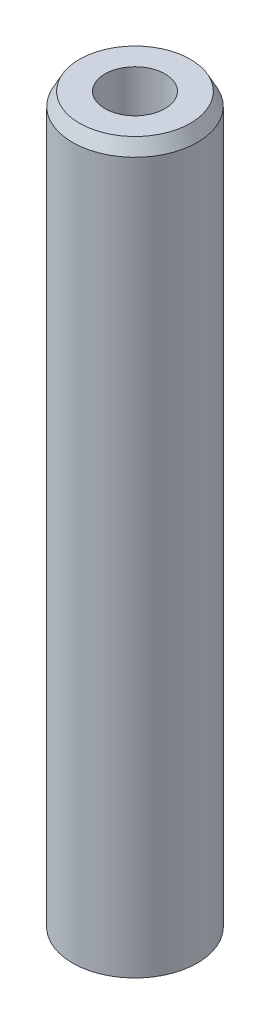
SolidWorks part; units mm, degrees
ref_plane "Front Plane" through (0, 0, 0) normal (0, 0, 1) x (1, 0, 0)
ref_plane "Top Plane" through (0, 0, 0) normal (0, 1, 0) x (1, 0, 0)
ref_plane "Right Plane" through (0, 0, 0) normal (1, 0, 0) x (0, 0, -1)
sketch "Sketch1" plane through (0, 0, 0) normal (0, 1, 0) x (1, 0, 0)
  circle A0 centre (0, 0) radius 17.5
  dimension "SHAFT_OD" = 35
extrude "Boss-Extrude1" add sketch "Sketch1" along normal blind 204.7804
sketch "Sketch2" plane through (0, 0, 0) normal (0, 1, 0) x (1, 0, 0)
  circle A0 centre (0, 0) radius 8.4297
  dimension "BORE_D" = 16.8593
extrude "Cut-Extrude1" cut sketch "Sketch2" along normal through all
chamfer "Chamfer1" distance 3.6586 angle 28.232 2 edges at (0, 204.7804, 17.5) (0, 0, 17.5) first distance on face at (0, 204.7804, 17.5) first distance on face at (0, 0, 8.4297)
